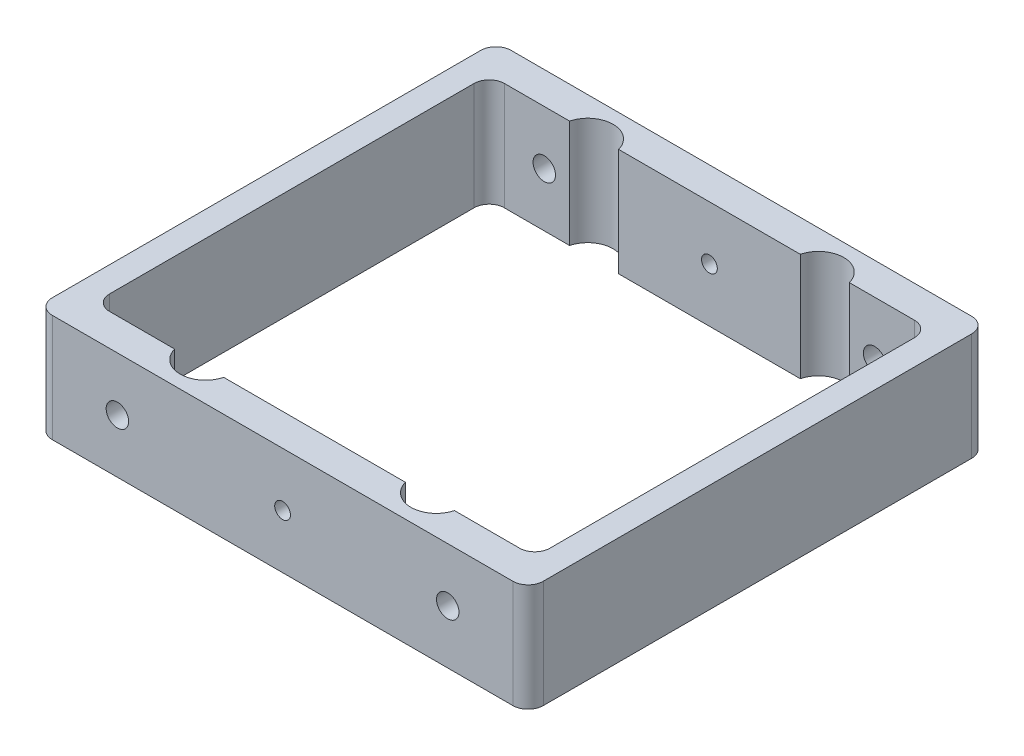
SolidWorks part; units mm, degrees
ref_plane "Front Plane" through (0, 0, 0) normal (0, 0, 1) x (1, 0, 0)
ref_plane "Top Plane" through (0, 0, 0) normal (0, 1, 0) x (1, 0, 0)
ref_plane "Right Plane" through (0, 0, 0) normal (1, 0, 0) x (0, 0, -1)
sketch "Sketch1" plane through (0, 0, 0) normal (0, 1, 0) x (1, 0, 0)
  line L1 (0, 0) -> (60, 0)
  line L2 (0, 0) -> (0, -6.32)
  line L3 (0, -6.32) -> (60, -6.32)
  line L4 (60, 0) -> (60, -6.32)
  dimension "D1" = 60
  dimension "D2" = 6.32
extrude "Boss-Extrude1" add sketch "Sketch1" along normal mid plane 21.28
sketch "Sketch2" plane through (0, 10.64, 0) normal (0, 1, 0) x (1, 0, 0)
  line L0 (0, 0) -> (0, -6.32) construction
  line L1 (0, -6.32) -> (60, -6.32) construction
  line L2 (60, -6.32) -> (60, 0) construction
  circle A0 centre (7.21, 1.25) radius 5
  circle A1 centre (52.79, 1.25) radius 5
  dimension "D1" = 7.21
  dimension "D3" = 7.21
  dimension "D2" = 7.57
  dimension "D4" = 7.57
extrude "Cut-Extrude1" cut sketch "Sketch2" against normal through all
sketch "Sketch3" plane through (60, 0, 0) normal (1, 0, 0) x (0, 0, -1)
  line L1 (-6.32, 10.64) -> (0, 10.64)
  line L2 (-6.32, 10.64) -> (-6.32, -10.64)
  line L3 (-6.32, -10.64) -> (0, -10.64)
  line L4 (0, 10.64) -> (0, -10.64)
extrude "Boss-Extrude2" add sketch "Sketch3" along normal blind 18.5
sketch "Sketch4" plane through (0, 0, 0) normal (-1, 0, 0) x (0, 0, 1)
  line L1 (0, 10.64) -> (6.32, 10.64)
  line L2 (0, 10.64) -> (0, -10.64)
  line L3 (0, -10.64) -> (6.32, -10.64)
  line L4 (6.32, 10.64) -> (6.32, -10.64)
extrude "Boss-Extrude3" add sketch "Sketch4" along normal blind 18.5
sketch "Sketch5" plane through (0, 0, 0) normal (0, 0, -1) x (-1, 0, 0)
  line L5 (-2.3688, -10.64) -> (18.5, -10.64) construction
  line L6 (18.5, 10.64) -> (13.5, 10.64)
  line L7 (18.5, 10.64) -> (18.5, -10.64)
  line L8 (18.5, -10.64) -> (13.5, -10.64)
  line L9 (13.5, 10.64) -> (13.5, -10.64)
  dimension "D1" = 5
extrude "Boss-Extrude6" add sketch "Sketch5" along normal blind 84.33
sketch "Sketch6" plane through (0, 0, 0) normal (0, 0, -1) x (-1, 0, 0)
  line L1 (-78.5, 10.64) -> (-73.5, 10.64)
  line L2 (-78.5, 10.64) -> (-78.5, -10.652)
  line L3 (-78.5, -10.652) -> (-73.5, -10.652)
  line L4 (-73.5, 10.64) -> (-73.5, -10.652)
  dimension "D1" = 5
extrude "Boss-Extrude7" add sketch "Sketch6" along normal blind 84.33
sketch "Sketch7" plane through (73.5, 0, 0) normal (-1, 0, 0) x (0, 0, 1)
  line L0 (-84.33, -10.652) -> (0, -10.652) construction
  line L1 (-84.33, 10.64) -> (-78.01, 10.64)
  line L2 (-84.33, 10.64) -> (-84.33, -10.652)
  line L3 (-84.33, -10.652) -> (-78.01, -10.652)
  line L4 (-78.01, 10.64) -> (-78.01, -10.652)
  dimension "D1" = 6.32
extrude "Boss-Extrude8" add sketch "Sketch7" along normal through all
sketch "Sketch9" plane through (0, 10.64, 0) normal (0, 1, 0) x (1, 0, 0)
  line L0 (-18.5, 84.33) -> (78.5, 84.33) construction
  circle A0 centre (7.21, 76.76) radius 5
  circle A1 centre (52.79, 76.76) radius 5
  dimension "D1" = 7.57
  dimension "D2" = 7.57
  dimension "D3" = 10
extrude "Cut-Extrude2" cut sketch "Sketch9" against normal through all
sketch "Sketch10" plane through (0, 0, -84.33) normal (0, 0, -1) x (-1, 0, 0)
  line L1 (-78.5, -10.64) -> (18.5, -10.64) construction
  line L2 (-30, -10.64) -> (-30, 10.64) construction
  line L3 (18.5, 10.64) -> (-78.5, 10.64) construction
  circle A0 centre (-62.6312, 0.005) radius 2.22
  circle A1 centre (2.6312, 0.005) radius 2.22
  dimension "D1" = 5
  dimension "D2" = 10.645
extrude "Cut-Extrude3" cut sketch "Sketch10" against normal through all
fillet "Fillet1" radius 3 8 edges at (-18.5, 0, 6.32) (78.5, 0, 6.32) (78.5, -0.006, -84.33) (-18.5, -0.006, -84.33) (-13.5, 0, -78.01) (-13.5, 0, 0) (73.5, -0.006, -78.01) (73.5, 0, 0)
sketch "Sketch13" plane through (0, 0, -84.33) normal (0, 0, -1) x (-1, 0, 0)
  line L1 (-75.5, 10.64) -> (-75.5, -10.652) construction
  line L2 (-75.5, -10.64) -> (15.5, -10.64) construction
  circle A0 centre (-30, 0.005) radius 1.555
  dimension "D1" = 45.5
  dimension "D2" = 10.645
extrude "Cut-Extrude4" cut sketch "Sketch13" against normal through all
